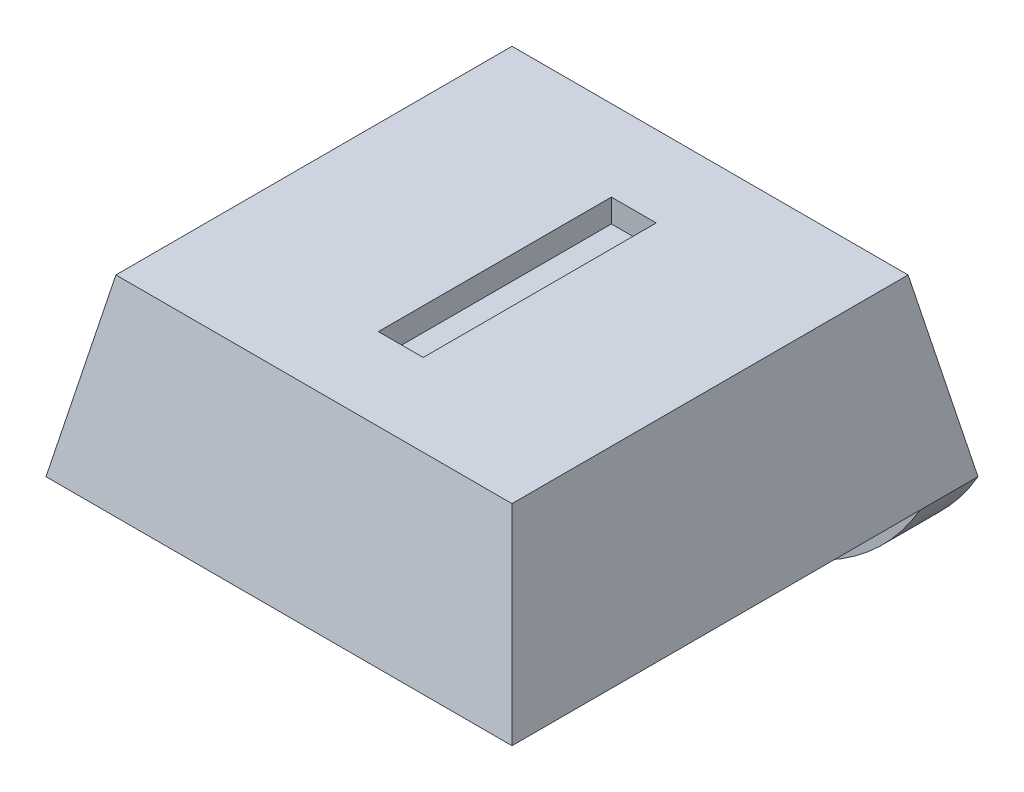
SolidWorks part; units mm, degrees
ref_plane "Front Plane" through (0, 0, 0) normal (0, 0, 1) x (1, 0, 0)
ref_plane "Top Plane" through (0, 0, 0) normal (0, 1, 0) x (1, 0, 0)
ref_plane "Right Plane" through (0, 0, 0) normal (1, 0, 0) x (0, 0, -1)
sketch "Sketch1" plane through (0, 0, 0) normal (0, 1, 0) x (1, 0, 0)
  line L1 (0, 0) -> (8, 0)
  line L2 (0, 0) -> (0, 8)
  line L3 (0, 8) -> (8, 8)
  line L4 (8, 0) -> (8, 8)
  dimension "D1" = 8
  dimension "D2" = 8
extrude "Boss-Extrude1" add sketch "Sketch1" along normal blind 3
sketch "Sketch2" plane through (0, 0, 0) normal (0, 0, 1) x (1, 0, 0)
  line L0 (0, 0) -> (0.6, 3)
  line L1 (0, 3) -> (8, 3) construction
  line L2 (0.6, 3) -> (0, 3)
  line L3 (0, 3) -> (0, 0)
  line L4 (8, 0) -> (7.4, 3)
  line L5 (7.4, 3) -> (8, 3)
  line L6 (8, 3) -> (8, 0)
  dimension "D1" = 0.6
  dimension "D2" = 0.6
extrude "Cut-Extrude1" cut sketch "Sketch2" against normal through all both and the other way through all
sketch "Sketch3" plane through (0, 0, 0) normal (1, 0, 0) x (0, 0, -1)
  line L0 (0, 0) -> (0.6, 3)
  line L1 (8, 3) -> (0, 3) construction
  line L2 (0.6, 3) -> (0, 3)
  line L3 (0, 3) -> (0, 0)
  line L4 (8, 3) -> (7.4, 3)
  line L5 (7.4, 3) -> (8, 0)
  line L6 (8, 3) -> (8, 0)
  dimension "D1" = 0.6
  dimension "D2" = 0.6
extrude "Cut-Extrude2" cut sketch "Sketch3" along normal blind 11
sketch "Sketch4" plane through (0, 0, 0) normal (0, -1, 0) x (1, 0, 0)
  line L0 (8, 0) -> (8, -8) construction
  line L3 (0, 0) -> (8, 0) construction
  circle A0 centre (4, -3.75) radius 1.8
  dimension "D1" = 3.6
  dimension "D2" = 4
  dimension "D3" = 3.75
extrude "Cut-Extrude3" cut sketch "Sketch4" against normal blind 0.8
sketch "Sketch5" plane through (0, 0, 0) normal (0, -1, 0) x (1, 0, 0)
  line L0 (8, 0) -> (8, -8) construction
  line L1 (0, -8) -> (8, -8)
  line L2 (0, -8) -> (0, -7)
  line L3 (0, -7) -> (8, -7)
  line L4 (8, -8) -> (8, -7)
  dimension "D1" = 1
extrude "Boss-Extrude2" add sketch "Sketch5" along normal blind 2
fillet "Fillet1" radius 4 2 edges at (8, -2, -7.5) (0, -2, -7.5)
sketch "Sketch6" plane through (0, 3, 0) normal (0, 1, 0) x (1, 0, 0)
  text T0 "I" font "Arial" height 4
extrude "Cut-Extrude4" cut sketch "Sketch6" against normal blind 0.4
